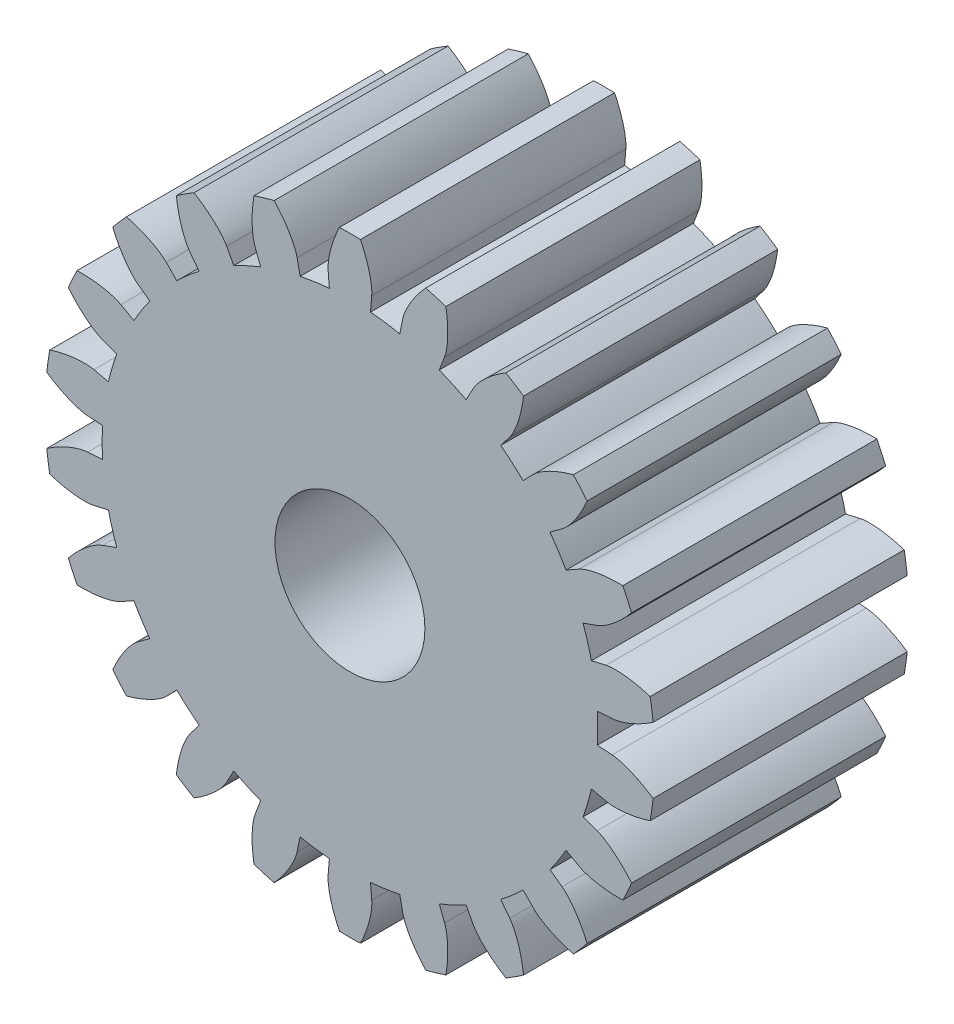
SolidWorks part; units mm, degrees
ref_plane "前视基准面" through (0, 0, 0) normal (0, 0, 1) x (1, 0, 0)
ref_plane "上视基准面" through (0, 0, 0) normal (0, 1, 0) x (1, 0, 0)
ref_plane "右视基准面" through (0, 0, 0) normal (1, 0, 0) x (0, 0, -1)
other "Configuration Table"
sketch "草图1" plane through (0, 0, 0) normal (0, 0, 1) x (1, 0, 0)
  line L0 (0, 0) -> (5.5, 0) construction
  line L1 (0, 0) -> (5.486, 0.3924) construction
  line L2 (0, 0) -> (5.1591, 0.3085)
  line L3 (5.486, 0.3924) -> (5.486, -0.3924) construction
  line L4 (0, 0) -> (5.1591, -0.3085)
  circle A0 centre (0, 0) radius 6
  circle A1 centre (0, 0) radius 5.5 construction
  circle A2 centre (0, 0) radius 4.875
  circle A3 centre (0, 0) radius 5.1683 construction
  circle A4 centre (0, 0) radius 1.475
  spline S0 degree 4 poles (5.1591, 0.3085) (5.1787, 0.3097) (5.2178, 0.3139) (5.3262, 0.3352) (5.5266, 0.4003) (5.8179, 0.5408) (6.1845, 0.792) (6.6046, 1.1791) (7.0235, 1.7012) (7.3966, 2.335) (7.7005, 3.0668) (7.9114, 3.83) (8.0349, 4.612) (8.0779, 5.4414) (8.0238, 6.4685) (7.8026, 7.6769) (7.3434, 9.0289) (6.6073, 10.4338) (5.6773, 11.7176) (4.583, 12.8638) (3.3517, 13.8606) (2.0089, 14.7006) (0.757, 15.2944) (-0.3576, 15.7013) (-1.3076, 15.9724) (-1.9821, 16.1267) (-2.5644, 16.2337) (-3.0541, 16.3061) (-3.444, 16.3541) (-3.8415, 16.3921) (-4.228, 16.4203) (-4.6004, 16.4369) (-4.9032, 16.4452) (-5.2491, 16.4466) (-5.4729, 16.4441) (-5.8345, 16.4347) (-6.1154, 16.4195) (-6.4564, 16.3977) (-6.7597, 16.37) (-7.0862, 16.3361) (-7.3953, 16.2963) (-7.6375, 16.2619) (-7.7916, 16.2371) (-7.8716, 16.2241) knots 0 0 0 0 0 0.002802 0.005604 0.015718 0.02996 0.048734 0.068727 0.096889 0.125051 0.153212 0.181374 0.209535 0.237696 0.271429 0.327752 0.384075 0.440398 0.496721 0.553044 0.609367 0.66569 0.722013 0.750174 0.778336 0.806497 0.820578 0.834659 0.84874 0.86282 0.876901 0.890982 0.900036 0.909091 0.920455 0.931818 0.943182 0.954545 0.965909 0.977273 0.988636 1 1 1 1 1 construction
  spline S1 degree 4 poles (5.1591, 0.3085) (5.1787, 0.3097) (5.2178, 0.3139) (5.3262, 0.3352) (5.5266, 0.4003) (5.8179, 0.5408) (6.1845, 0.792) (6.6046, 1.1791) (7.0235, 1.7012) (7.3966, 2.335) (7.7005, 3.0668) (7.9114, 3.83) (8.0349, 4.612) (8.0779, 5.4414) (8.0238, 6.4685) (7.8026, 7.6769) (7.3434, 9.0289) (6.6073, 10.4338) (5.6773, 11.7176) (4.583, 12.8638) (3.3517, 13.8606) (2.0089, 14.7006) (0.757, 15.2944) (-0.3576, 15.7013) (-1.3076, 15.9724) (-1.9821, 16.1267) (-2.5644, 16.2337) (-3.0541, 16.3061) (-3.444, 16.3541) (-3.8415, 16.3921) (-4.228, 16.4203) (-4.6004, 16.4369) (-4.9032, 16.4452) (-5.1588, 16.4462) (-5.2753, 16.4458) (-5.333, 16.4452) knots 0 0 0 0 0 0.002802 0.005604 0.015718 0.02996 0.048734 0.068727 0.096889 0.125051 0.153212 0.181374 0.209535 0.237696 0.271429 0.327752 0.384075 0.440398 0.496721 0.553044 0.609367 0.66569 0.722013 0.750174 0.778336 0.806497 0.820578 0.834659 0.84874 0.86282 0.876901 0.890982 0.900036 0.909091 0.909091 0.909091 0.909091 0.909091
  spline S2 degree 4 poles (5.1591, -0.3085) (5.1787, -0.3097) (5.2178, -0.3139) (5.3262, -0.3352) (5.5266, -0.4003) (5.8179, -0.5408) (6.1845, -0.792) (6.6046, -1.1791) (7.0235, -1.7012) (7.3966, -2.335) (7.7005, -3.0668) (7.9114, -3.83) (8.0349, -4.612) (8.0779, -5.4414) (8.0238, -6.4685) (7.8026, -7.6769) (7.3434, -9.0289) (6.6073, -10.4338) (5.6773, -11.7176) (4.583, -12.8638) (3.3517, -13.8606) (2.0089, -14.7006) (0.757, -15.2944) (-0.3576, -15.7013) (-1.3076, -15.9724) (-1.9821, -16.1267) (-2.5644, -16.2337) (-3.0541, -16.3061) (-3.444, -16.3541) (-3.8415, -16.3921) (-4.228, -16.4203) (-4.6004, -16.4369) (-4.9032, -16.4452) (-5.2491, -16.4466) (-5.4729, -16.4441) (-5.8345, -16.4347) (-6.1154, -16.4195) (-6.4564, -16.3977) (-6.7597, -16.37) (-7.0862, -16.3361) (-7.3953, -16.2963) (-7.6375, -16.2619) (-7.7916, -16.2371) (-7.8716, -16.2241) knots 0 0 0 0 0 0.002802 0.005604 0.015718 0.02996 0.048734 0.068727 0.096889 0.125051 0.153212 0.181374 0.209535 0.237696 0.271429 0.327752 0.384075 0.440398 0.496721 0.553044 0.609367 0.66569 0.722013 0.750174 0.778336 0.806497 0.820578 0.834659 0.84874 0.86282 0.876901 0.890982 0.900036 0.909091 0.920455 0.931818 0.943182 0.954545 0.965909 0.977273 0.988636 1 1 1 1 1 construction
  spline S3 degree 4 poles (5.1591, -0.3085) (5.1787, -0.3097) (5.2178, -0.3139) (5.3262, -0.3352) (5.5266, -0.4003) (5.8179, -0.5408) (6.1845, -0.792) (6.6046, -1.1791) (7.0235, -1.7012) (7.3966, -2.335) (7.7005, -3.0668) (7.9114, -3.83) (8.0349, -4.612) (8.0779, -5.4414) (8.0238, -6.4685) (7.8026, -7.6769) (7.3434, -9.0289) (6.6073, -10.4338) (5.6773, -11.7176) (4.583, -12.8638) (3.3517, -13.8606) (2.0089, -14.7006) (0.757, -15.2944) (-0.3576, -15.7013) (-1.3076, -15.9724) (-1.9821, -16.1267) (-2.5644, -16.2337) (-3.0541, -16.3061) (-3.444, -16.3541) (-3.8415, -16.3921) (-4.228, -16.4203) (-4.6004, -16.4369) (-4.9032, -16.4452) (-5.1588, -16.4462) (-5.2753, -16.4458) (-5.333, -16.4452) knots 0 0 0 0 0 0.002802 0.005604 0.015718 0.02996 0.048734 0.068727 0.096889 0.125051 0.153212 0.181374 0.209535 0.237696 0.271429 0.327752 0.384075 0.440398 0.496721 0.553044 0.609367 0.66569 0.722013 0.750174 0.778336 0.806497 0.820578 0.834659 0.84874 0.86282 0.876901 0.890982 0.900036 0.909091 0.909091 0.909091 0.909091 0.909091
  point P15 (5.486, 0)
  dimension "齿顶圆直径" = 12
  dimension "分度圆直径" = 11
  dimension "齿根圆直径" = 9.75
  dimension "基圆直径" = 10.3366
  dimension "内孔直径" = 2.95
  dimension "渐近线镜像线夹角" = 4.091
extrude "凸台-拉伸1" add sketch "草图1" along normal blind 5 contours A0 | A4
extrude "切除-拉伸1" cut sketch "草图1<3>" along normal through all contours A2 S3 A0 S1 region at (5.5142, 0, 0)
sketch "草图1<3>" plane through (0, 0, 0) normal (0, 0, 1) x (1, 0, 0) same geometry as "草图1"
pattern_circular "阵列(圆周)1" count 22 every 16.364 about axis through (0, 0, 5) along (0, 0, 1) of "切除-拉伸1"
equation "\"m\"= 0.5'模数"
equation "\"z\"= 22'齿数"
equation "\"a\"= 20度'压力角"
equation "\"d\"= \"m\" * \"z\"'分度圆直径"
equation "\"da\"= ( \"z\" + 2 ) * \"m\"'齿顶圆直径"
equation "\"df\"= ( \"z\" - 2.5 ) * \"m\"'齿根圆直径"
equation "\"s\"= 0.5 * PI * \"m\"'分度圆齿厚"
equation "\"r\"= 0.38 * \"m\"'齿根圆角"
equation "\"B\"= 0.3 * \"d\"'齿厚"
equation "\"db\"= \"m\" * \"z\" * cos ( \"a\" )'基圆直径"
equation "\"rb\"= \"db\" / 2'基圆半径"
equation "\"齿顶圆直径@草图1\"= \"da\""
equation "\"分度圆直径@草图1\"= \"d\""
equation "\"齿根圆直径@草图1\"= \"df\""
equation "\"基圆直径@草图1\"= \"db\""
equation "\"渐近线镜像线夹角@草图1\"= 360 / 4 / \"z\""
equation "\"h\"= 5'齿轮厚度"
equation "\"ir\"= 2.95'内孔直径"
equation "\"内孔直径@草图1\"= \"ir\""
equation "\"齿轮厚@凸台-拉伸1\"= \"h\""
equation "\"齿轮夹角@阵列(圆周)1\"= 360 / \"z\""
equation "\"齿数@阵列(圆周)1\"= \"z\""
